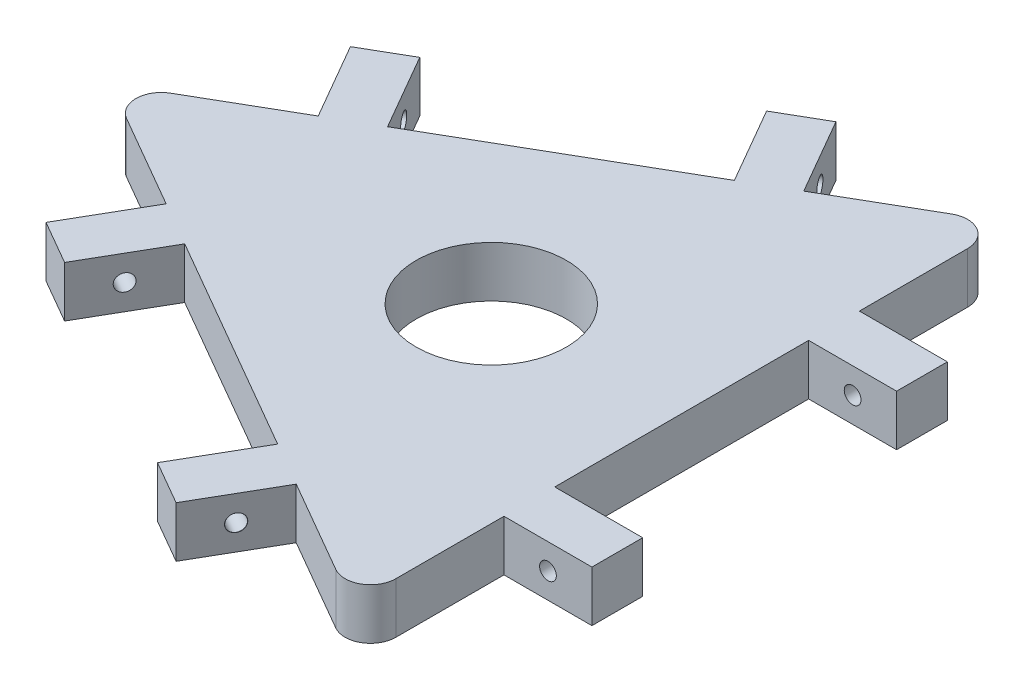
SolidWorks part; units mm, degrees
material "PLA"
ref_plane "Front" through (0, 0, 0) normal (0, 0, 1) x (1, 0, 0)
ref_plane "Top" through (0, 0, 0) normal (0, 1, 0) x (1, 0, 0)
ref_plane "Right" through (0, 0, 0) normal (1, 0, 0) x (0, 0, -1)
sketch "Sketch2" plane through (0, 0, 0) normal (0, 1, 0) x (0, 0, -1)
  line L0 (0, 0) -> (0, 70) construction
  line L1 (0, 0) -> (-60.6218, -35) construction
  line L2 (-60.6218, -30) -> (-49.976, -11.5609)
  line L3 (4.3301, 67.5) -> (14.976, 49.0609)
  line L4 (56.2917, -37.5) -> (35, -37.5)
  line L5 (0, 0) -> (-23.8157, 13.75) construction
  line L9 (-49.976, -11.5609) -> (-64.976, -2.9006)
  line L10 (-44.976, -2.9006) -> (-59.976, 5.7596)
  line L11 (-64.976, -2.9006) -> (-59.976, 5.7596)
  line L12 (-19.976, 40.4006) -> (-34.976, 49.0609)
  line L13 (-29.976, 57.7211) -> (-34.976, 49.0609)
  line L14 (-14.976, 49.0609) -> (-29.976, 57.7211)
  line L17 (14.976, 49.0609) -> (29.976, 57.7211)
  line L18 (29.976, 57.7211) -> (34.976, 49.0609)
  line L19 (19.976, 40.4006) -> (34.976, 49.0609)
  line L20 (44.976, -2.9006) -> (59.976, 5.7596)
  line L21 (64.976, -2.9006) -> (59.976, 5.7596)
  line L22 (49.976, -11.5609) -> (64.976, -2.9006)
  line L25 (35, -37.5) -> (35, -54.8205)
  line L26 (35, -54.8205) -> (25, -54.8205)
  line L27 (25, -37.5) -> (25, -54.8205)
  line L28 (-35, -37.5) -> (-35, -54.8205)
  line L29 (-35, -54.8205) -> (-25, -54.8205)
  line L30 (-25, -37.5) -> (-25, -54.8205)
  line L32 (-44.976, -2.9006) -> (-19.976, 40.4006)
  line L33 (-14.976, 49.0609) -> (-4.3301, 67.5)
  line L34 (19.976, 40.4006) -> (44.976, -2.9006)
  line L35 (49.976, -11.5609) -> (60.6218, -30)
  line L36 (25, -37.5) -> (-25, -37.5)
  line L37 (-35, -37.5) -> (-56.2917, -37.5)
  line L38 (-49.976, -11.5609) -> (-44.976, -2.9006)
  line L39 (-14.976, 49.0609) -> (-19.976, 40.4006)
  line L40 (14.976, 49.0609) -> (19.976, 40.4006)
  line L41 (49.976, -11.5609) -> (44.976, -2.9006)
  line L42 (35, -37.5) -> (25, -37.5)
  line L43 (-35, -37.5) -> (-25, -37.5)
  arc A0 (-60.6218, -30) -> (-56.2917, -37.5) centre (-56.2917, -32.5) ccw
  arc A1 (60.6218, -30) -> (56.2917, -37.5) centre (56.2917, -32.5) cw
  arc A2 (4.3301, 67.5) -> (-4.3301, 67.5) centre (0, 65) ccw
  circle A3 centre (-56.2917, -32.5) radius 5 construction
  circle A4 centre (0, 0) radius 14.7988
  dimension "D4" = 10
  dimension "D1" = 29.5977
  dimension "D2" = 50
  dimension "D3" = 70
  dimension "D7" = 10
  dimension "D8" = 15
extrude "Boss-Extrude1" add sketch "Sketch2" along normal blind 10 contours L3 A2 L33 L39 L32 L38 L2 A0 L37 L43 L36 L42 L4 A1 L35 L41 L34 L40 region at (21.5957, 0, 53.8869)
extrude "Boss-Extrude3" add sketch "Sketch2<7>" along normal blind 10 contours L41 L22 L21 L20 | L17 L40 L19 L18 region at (-49.0609, 0, -24.976) region at (2.9006, 0, -54.976)
sketch "Sketch2<7>" plane through (0, 0, 0) normal (0, 1, 0) x (0, 0, -1) same geometry as "Sketch2"
sketch "Sketch10" plane through (-30.3109, 0, 17.5) normal (-0.866, 0, 0.5) x (0.5, 0, 0.866)
  line L1 (-46.1603, 5) -> (-37.5, 5) construction
  line L2 (-54.8205, 5) -> (-46.1603, 5) construction
  line L9 (-54.8205, 10) -> (-54.8205, 0) construction
  line L11 (-46.1603, 5) -> (-46.1603, 10) construction
  line L12 (-37.5, 10) -> (-54.8205, 10) construction
  line L14 (-46.1603, 5) -> (-46.1603, 0) construction
  line L15 (-37.5, 0) -> (-54.8205, 0) construction
  point P0 (-46.1603, 5)
  dimension "D1" = 180
hole_wizard "Tap Drill for M4 Tap1" positions "Sketch10" profile "Sketch11" hole size "M4" standard "ISO" end condition through all
sketch "Sketch11" plane through (-53.391, 5, -22.476) normal (0, 1, 0) x (0.5, 0, 0.866)
  line L0 (0, 0) -> (0, 99.9639)
  line L1 (0, 99.9639) -> (1.65, 99.9639)
  line L2 (1.65, 99.9639) -> (1.65, 0.025)
  line L3 (1.65, 0.025) -> (1.675, 0)
  line L5 (1.675, 0) -> (0, 0)
  line L6 (-1.65, 0.025) -> (-1.675, 0) construction
  line L11 (0, -6.35) -> (0, 107.95) construction
  dimension "Thru Hole Dia." = 3.3
  dimension "Thru Hole Depth" = 99.9639
  dimension "Near C'Sink Dia." = 3.35
  dimension "Near C'Sink Angle" = 90
pattern_circular "CirPattern1" count 3 every 120 about axis through (0, 10, 0) along (0, 1, 0) of "Boss-Extrude3", "Tap Drill for M4 Tap1"
